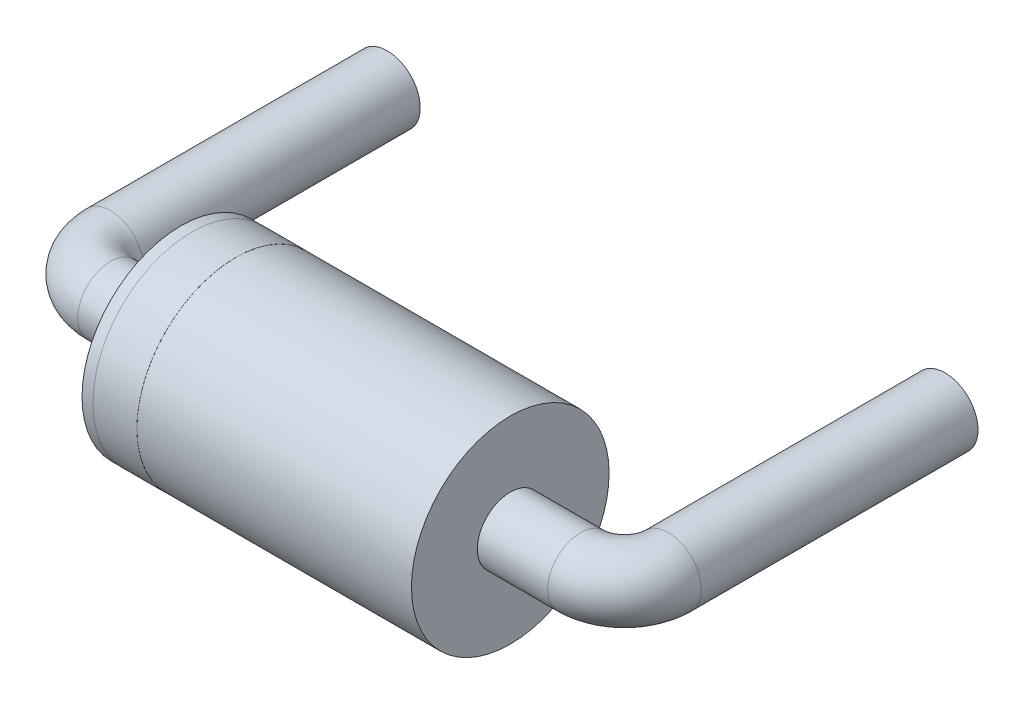
SolidWorks part; units mm, degrees
ref_plane "Ön Düzlem" through (0, 0, 0) normal (0, 0, 1) x (1, 0, 0)
ref_plane "Üst Düzlem" through (0, 0, 0) normal (0, 1, 0) x (1, 0, 0)
ref_plane "Sağ Düzlem" through (0, 0, 0) normal (1, 0, 0) x (0, 0, -1)
ref_plane "Düzlem1" through (0, 0, -2) normal (0, 0, -1) x (-1, 0, 0)
sketch "Çizim2" plane through (0, 0, -2) normal (0, 0, -1) x (-1, 0, 0)
  line L0 (-2.54, 0) -> (2.54, 0) construction
  circle A0 centre (-2.54, 0) radius 0.3
  dimension "D2" = 0.6
  dimension "D1" = 5.08
sketch "Çizim3" plane through (0, 0, 0) normal (0, 1, 0) x (1, 0, 0)
  line L0 (2.54, 2) -> (2.54, -0.52)
  line L1 (2.14, -0.92) -> (-2.14, -0.92)
  line L2 (-2.54, -0.52) -> (-2.54, 2)
  line L3 (2.54, 2) -> (-2.54, 2) construction
  line L4 (0.9911, 2) -> (-0.9911, 2) construction
  arc A0 (-2.14, -0.92) -> (-2.54, -0.52) centre (-2.14, -0.52) cw
  arc A1 (2.54, -0.52) -> (2.14, -0.92) centre (2.14, -0.52) cw
  point P12 (5.08, 2)
  dimension "D2" = 0.4
  dimension "D1" = 2.92
sweep "Süpür2" add profiles "Çizim2" path "Çizim3"
sketch "Çizim4" plane through (0, 0, 0) normal (1, 0, 0) x (0, 0, -1)
  circle A0 centre (-0.92, 0) radius 0.9
  dimension "D1" = 1.8
extrude "Yükseklik-Ekstrüzyon3" add sketch "Çizim4" against normal mid plane 3 contours A0
sketch "Çizim7" plane through (0, 0, 0) normal (-1, 0, 0) x (0, 0, 1)
  circle A0 centre (0.92, 0) radius 0.5
  dimension "D1" = 1
extrude "Ekstrüzyon-İnce1" add sketch "Çizim4<5>" along normal mid plane 0.4 from offset 1.2 thin contours A0 offset against normal yes thin type one direction wall 0.001
sketch "Çizim4<5>" plane through (0, 0, 0) normal (1, 0, 0) x (0, 0, -1) same geometry as "Çizim4"
